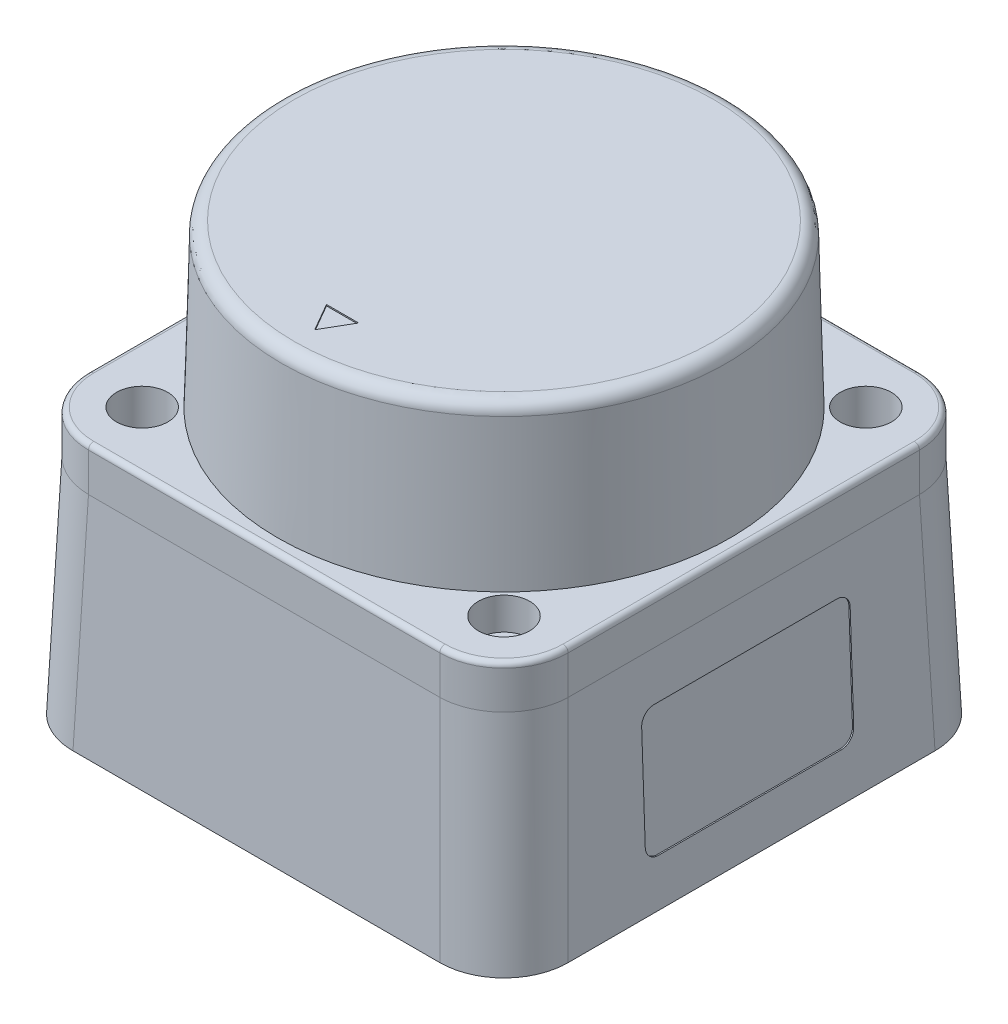
SolidWorks part; units mm, degrees
ref_plane "Front Plane" through (0, 0, 0) normal (0, 0, 1) x (1, 0, 0)
ref_plane "Top Plane" through (0, 0, 0) normal (0, 1, 0) x (1, 0, 0)
ref_plane "Right Plane" through (0, 0, 0) normal (1, 0, 0) x (0, 0, -1)
sketch "Sketch1" plane through (0, 0, 0) normal (0, 1, 0) x (1, 0, 0)
  line L0 (-19.295, 0) -> (19.295, 0) construction
  line L1 (-19.295, 19.295) -> (19.295, 19.295)
  line L2 (-19.295, 19.295) -> (-19.295, -19.295)
  line L3 (-19.295, -19.295) -> (19.295, -19.295)
  line L4 (19.295, 19.295) -> (19.295, -19.295)
  line L5 (0, 19.295) -> (0, -19.295) construction
  point P8 (0, 0)
  dimension "D1" = 38.59
  dimension "D2" = 38.59
extrude "Boss-Extrude1" add sketch "Sketch1" along normal blind 17.3 draft 2
sketch "Sketch2" plane through (0, 17.3, 0) normal (0, 1, 0) x (1, 0, 0)
  line L0 (0, 18.6909) -> (0, -18.6909) construction
  line L1 (-18.6909, 18.6909) -> (18.6909, 18.6909)
  line L2 (-18.6909, 18.6909) -> (-18.6909, -18.6909)
  line L3 (-18.6909, -18.6909) -> (18.6909, -18.6909)
  line L4 (18.6909, 18.6909) -> (18.6909, -18.6909)
  line L5 (-18.6909, 0) -> (18.6909, 0) construction
  line L6 (18.6909, -18.6909) -> (18.6909, 18.6909) construction
  line L7 (18.6909, 18.6909) -> (-18.6909, 18.6909) construction
  point P8 (0, 0)
extrude "Boss-Extrude2" add sketch "Sketch2" along normal blind 3.4
sketch "Sketch3" plane through (0, 20.7, 0) normal (0, 1, 0) x (1, 0, 0)
  circle A0 centre (0, 0) radius 17.645
  dimension "D1" = 35.29
extrude "Boss-Extrude3" add sketch "Sketch3" along normal blind 12.6 draft 1.5 contours A0
fillet "Fillet1" radius 5 8 edges at (-18.9929, 8.65, -18.9929) (-18.6909, 19, -18.6909) (18.6909, 19, -18.6909) (18.9929, 8.65, -18.9929) (-18.9929, 8.65, 18.9929) (-18.6909, 19, 18.6909) (18.9929, 8.65, 18.9929) (18.6909, 19, 18.6909)
fillet "Fillet2" radius 0.4 8 edges at (17.2264, 20.7, -17.2264) (0, 20.7, -18.6909) (18.6909, 20.7, 0) (17.2264, 20.7, 17.2264) (0, 20.7, 18.6909) (-17.2264, 20.7, 17.2264) (-18.6909, 20.7, 0) (-17.2264, 20.7, -17.2264)
fillet "Fillet3" radius 1 1 edges at (0, 33.3, 17.3151)
sketch "Sketch4" plane through (0, 33.3, 0) normal (0, 1, 0) x (1, 0, 0)
  line L1 (0, -14.75) -> (1.25, -12.5849)
  line L2 (1.25, -12.5849) -> (-1.25, -12.5849)
  line L3 (-1.25, -12.5849) -> (0, -14.75)
  circle A0 centre (0, -13.3066) radius 1.4434 construction
  dimension "D1" = 14.75
  dimension "D2" = 2.5
extrude "Cut-Extrude1" cut sketch "Sketch4" against normal blind 0.1
sketch "Sketch5" plane through (0, 0, 0) normal (0, 0, 1) x (1, 0, 0)
  line L0 (16.3409, 33.3) -> (-16.3409, 33.3) construction
  circle A0 centre (0, 25.7) radius 4
  dimension "D1" = 7.6
  dimension "D2" = 8
extrude "Cut-Extrude2" [suppressed] cut sketch "Sketch5" against normal blind 0.01 from surface starting at face at (0, 32.3262, -17.3406)
sketch "Sketch6" plane through (0, 0, 0) normal (1, 0, 0) x (0, 0, -1)
  line L0 (-4.625, 3.725) -> (4.625, 3.725) construction
  line L1 (-4.625, 5.85) -> (4.625, 5.85)
  line L2 (-4.625, 5.85) -> (-4.625, 1.6)
  line L3 (-4.625, 1.6) -> (4.625, 1.6)
  line L4 (4.625, 5.85) -> (4.625, 1.6)
  line L5 (0, 5.85) -> (0, 1.6) construction
  line L6 (-14.298, 0) -> (14.298, 0) construction
  point P8 (0, 3.725)
  dimension "D1" = 9.25
  dimension "D2" = 4.25
  dimension "D3" = 1.6
extrude "Cut-Extrude3" cut sketch "Sketch6" along normal blind 7 from offset 19.295 offset against normal yes
sketch "Sketch15" plane through (0, 0, 0) normal (1, 0, 0) x (0, 0, -1)
  line L0 (-8.125, 8.6) -> (8.125, 8.6) construction
  line L1 (-8.125, 13.6) -> (8.125, 13.6)
  line L2 (-8.125, 13.6) -> (-8.125, 3.6)
  line L3 (-8.125, 3.6) -> (8.125, 3.6)
  line L4 (8.125, 13.6) -> (8.125, 3.6)
  line L5 (0, 13.6) -> (0, 3.6) construction
  line L6 (-14.298, 0) -> (14.298, 0) construction
  point P8 (0, 8.6)
  dimension "D1" = 3.6
  dimension "D2" = 10
  dimension "D3" = 16.25
extrude "Cut-Extrude4" cut sketch "Sketch15" against normal blind 0.1 from surface starting at face at (18.8922, 11.5333, 0)
fillet "Fillet4" radius 1 4 edges at (19.1193, 3.6, -8.125) (18.7701, 13.6, -8.125) (18.7701, 13.6, 8.125) (19.1193, 3.6, 8.125)
sketch "Sketch10" plane through (0, 20.7, 0) normal (0, 1, 0) x (1, 0, 0)
  line L0 (0, 18.2909) -> (0, -18.2909) construction
  line L1 (13.6909, 18.2909) -> (-13.6909, 18.2909) construction
  line L2 (-13.6909, -18.2909) -> (13.6909, -18.2909) construction
  line L3 (18.2909, 0) -> (-18.2909, 0) construction
  line L4 (18.2909, -13.6909) -> (18.2909, 13.6909) construction
  line L5 (-18.2909, 13.6909) -> (-18.2909, -13.6909) construction
  circle A0 centre (-14.1, 14.1) radius 2
  circle A1 centre (14.1, -14.1) radius 2
  dimension "D1" = 14.1
  dimension "D5" = 4
  dimension "D2" = 14.1
  dimension "D3" = 14.1
  dimension "D4" = 14.1
extrude "Cut-Extrude5" cut sketch "Sketch10" against normal blind 2.5
sketch "Sketch12" plane through (0, 18.2, 0) normal (0, 1, 0) x (1, 0, 0)
  circle A0 centre (14.1, -14.1) radius 1
  circle A1 centre (-14.1, 14.1) radius 1
  circle A2 centre (-14.1, 14.1) radius 2 construction
  circle A3 centre (14.1, -14.1) radius 2 construction
  dimension "D1" = 2
extrude "Cut-Extrude6" cut sketch "Sketch12" against normal blind 6
sketch "Sketch7" plane through (0, 20.7, 0) normal (0, 1, 0) x (1, 0, 0)
  line L0 (0, 18.2909) -> (0, -18.2909) construction
  line L1 (13.6909, 18.2909) -> (-13.6909, 18.2909) construction
  line L2 (-13.6909, -18.2909) -> (13.6909, -18.2909) construction
  line L3 (18.2909, 0) -> (-18.2909, 0) construction
  line L4 (18.2909, -13.6909) -> (18.2909, 13.6909) construction
  line L5 (-18.2909, 13.6909) -> (-18.2909, -13.6909) construction
  circle A0 centre (-14.1, -14.1) radius 2
  circle A1 centre (14.1, 14.1) radius 2
  dimension "D1" = 4
  dimension "D3" = 14.1
  dimension "D4" = 14.1
  dimension "D5" = 14.1
  dimension "D6" = 14.1
extrude "Cut-Extrude7" cut sketch "Sketch7" against normal blind 7.9
sketch "Sketch13" plane through (0, 12.8, 0) normal (0, 1, 0) x (1, 0, 0)
  circle A0 centre (-14.1, -14.1) radius 1.25
  circle A1 centre (-14.1, -14.1) radius 2 construction
  circle A2 centre (14.1, 14.1) radius 1.25
  circle A3 centre (14.1, 14.1) radius 2 construction
  dimension "D1" = 2.5
extrude "Cut-Extrude8" cut sketch "Sketch13" against normal blind 1
sketch "Sketch14" plane through (0, 11.8, 0) normal (0, 1, 0) x (1, 0, 0)
  circle A0 centre (-14.1, -14.1) radius 2.4
  circle A1 centre (-14.1, -14.1) radius 1.25 construction
  circle A2 centre (14.1, 14.1) radius 2.4
  circle A3 centre (14.1, 14.1) radius 1.25 construction
  dimension "D1" = 4.8
extrude "Cut-Extrude9" cut sketch "Sketch14" against normal blind 11.8
sketch "Sketch16" plane through (0, 0, 0) normal (0, -1, 0) x (1, 0, 0)
  line L0 (0, 19.295) -> (0, -19.295) construction
  line L1 (-14.298, 19.295) -> (14.298, 19.295) construction
  line L2 (14.298, -19.295) -> (-14.298, -19.295) construction
  line L3 (19.295, 0) -> (-19.295, 0) construction
  line L4 (19.295, 14.298) -> (19.295, -14.298) construction
  line L5 (-19.295, -14.298) -> (-19.295, 14.298) construction
  circle A0 centre (-15.7, -15.7) radius 1.25
  dimension "D1" = 2.5
  dimension "D2" = 15.7
  dimension "D3" = 15.7
extrude "Cut-Extrude10" cut sketch "Sketch16" against normal blind 5.8
